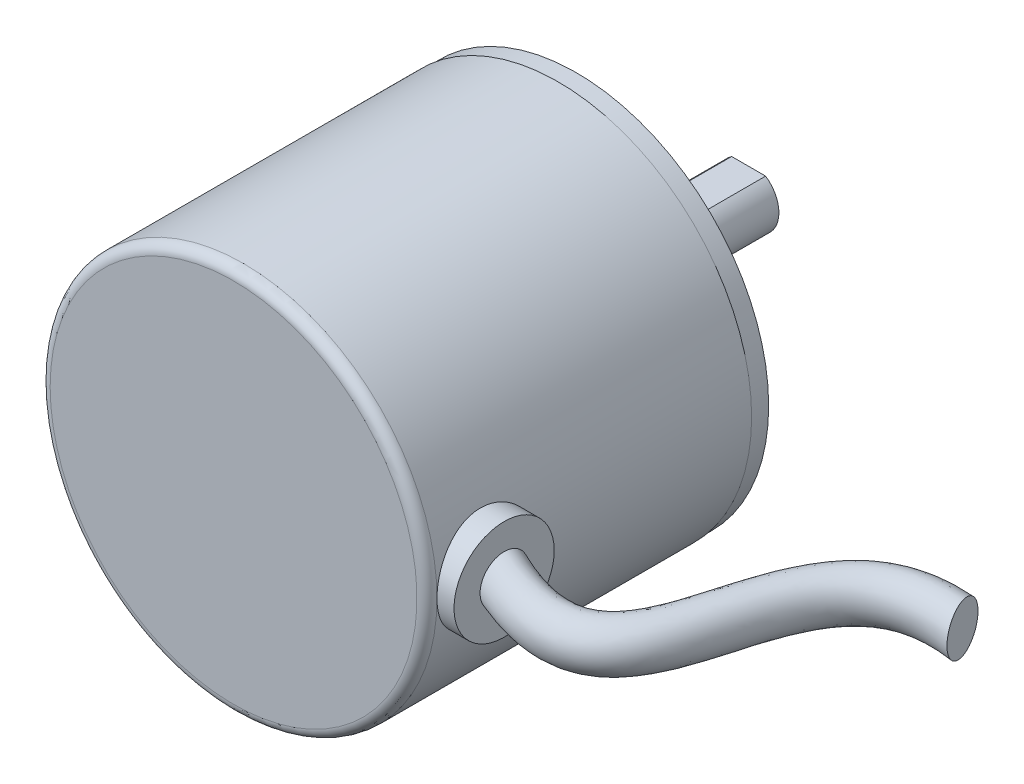
SolidWorks part; units mm, degrees
ref_plane "Front Plane" through (0, 0, 0) normal (0, 0, 1) x (1, 0, 0)
ref_plane "Top Plane" through (0, 0, 0) normal (0, 1, 0) x (1, 0, 0)
ref_plane "Right Plane" through (0, 0, 0) normal (1, 0, 0) x (0, 0, -1)
sketch "Sketch1" plane through (0, 0, 0) normal (1, 0, 0) x (0, 0, -1)
  line L0 (0, 0) -> (64.5458, 0) construction
  line L1 (0, 0) -> (0, 19.3)
  line L2 (0, 19.3) -> (32.4, 19.3)
  line L3 (32.4, 19.3) -> (32.4, 19.2)
  line L4 (34.2, 10.01) -> (39.4, 10.01)
  line L5 (39.4, 10.01) -> (39.4, 7.5)
  line L6 (39.4, 7.5) -> (37.9, 7.5)
  line L7 (37.9, 7.5) -> (37.9, 3.02)
  line L8 (37.9, 3.02) -> (51.4, 3.02)
  line L9 (51.4, 3.02) -> (51.4, 0)
  line L10 (32.4, 19.2) -> (34.2, 19.2)
  line L11 (34.2, 19.2) -> (34.2, 10.01)
  line L12 (0, 0) -> (51.4, 0)
  dimension "D1" = 6.04
  dimension "D2" = 20.02
  dimension "D3" = 38.6
  dimension "D4" = 38.4
  dimension "D5" = 1.8
  dimension "D6" = 34.2
  dimension "D7" = 5.2
  dimension "D8" = 51.4
  dimension "D9" = 1.5
  dimension "D10" = 15
revolve "Revolve1" add sketch "Sketch1" angle 360 about L0
sketch "Sketch2" plane through (0, 0, 0) normal (0, 1, 0) x (1, 0, 0)
  line L0 (3.02, 51.4) -> (-3.02, 51.4) construction
  line L1 (-7.5, 61.4) -> (7.5, 61.4)
  line L2 (-7.5, 61.4) -> (-7.5, 41.4)
  line L3 (-7.5, 41.4) -> (7.5, 41.4)
  line L4 (7.5, 61.4) -> (7.5, 41.4)
  line L5 (-7.5, 61.4) -> (7.5, 41.4) construction
  line L6 (-7.5, 41.4) -> (7.5, 61.4) construction
  point P0 (0, 51.4)
  point P7 (7.5, 51.4)
  dimension "D1" = 10
  dimension "D2" = 15
extrude "Cut-Extrude1" cut sketch "Sketch2" along normal blind 10 from offset 2.5
sketch "Sketch3" plane through (0, 0, 0) normal (1, 0, 0) x (0, 0, -1)
  circle A0 centre (6, 0) radius 5
  dimension "D1" = 10
  dimension "D2" = 6
extrude "Boss-Extrude1" add sketch "Sketch3" along normal blind 21
sketch "Sketch4" plane through (0, 0, 0) normal (0, 1, 0) x (1, 0, 0)
  line L0 (21, 1) -> (21, 11) construction
  spline S0 degree 3 poles (21, 6) (41.812, -3.3539) (29.2413, 26.7307) (48.1067, 24.6321) knots 0 0 0 0 1 1 1 1
sketch "Sketch5" plane through (21, 0, 0) normal (1, 0, 0) x (0, 0, -1)
  circle A0 centre (6, 0) radius 2.4
  dimension "D1" = 4.8
sweep "Sweep1" add profiles "Sketch5" path "Sketch4"
fillet "Fillet1" radius 1 1 edges at (19.3, 0, 0)
sketch "Sketch6" plane through (0, 0, -34.2) normal (0, 0, -1) x (-1, 0, 0)
  circle A0 centre (0, 14.1) radius 1.25
  circle A1 centre (12.211, -7.05) radius 1.25
  circle A2 centre (-12.211, -7.05) radius 1.25
  point P9 (0, 0)
  dimension "D1" = 2.5
  dimension "D2" = 14.1
  dimension "D3" = 3
extrude "Cut-Extrude2" cut sketch "Sketch6" against normal blind 5
